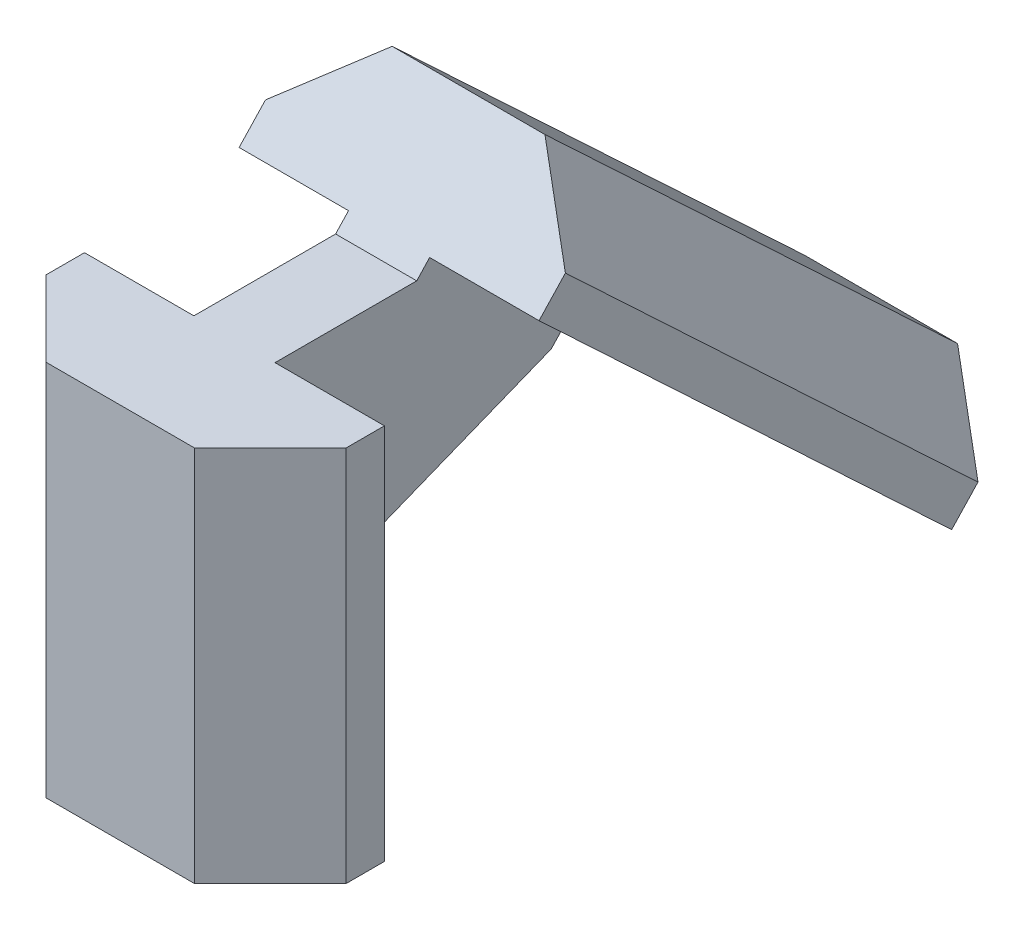
SolidWorks part; units mm, degrees
ref_plane "Front Plane" through (0, 0, 0) normal (0, 0, 1) x (1, 0, 0)
ref_plane "Top Plane" through (0, 0, 0) normal (0, 1, 0) x (1, 0, 0)
ref_plane "Right Plane" through (0, 0, 0) normal (1, 0, 0) x (0, 0, -1)
sketch "Sketch1" plane through (0, 0, 0) normal (0, 1, 0) x (1, 0, 0)
  line L0 (-3.9407, -6.0493) -> (3.9407, -6.0493)
  line L1 (7.95, 0) -> (7.95, -2.04)
  line L2 (7.95, -2.04) -> (3.9407, -6.0493)
  line L4 (0, 0) -> (0, 4.5954) construction
  line L5 (-7.95, -2.04) -> (-3.9407, -6.0493)
  line L6 (-7.95, 0) -> (-7.95, -2.04)
  line L7 (-7.95, 0) -> (7.95, 0)
  point P6 (3.7791, -6.0493)
  dimension "D1" = 15.9
  dimension "D2" = 2.04
  dimension "D3" = 5.67
extrude "Boss-Extrude1" add sketch "Sketch1" against normal blind 20 contours L7 L1 L2 L0 L5 L6
ref_plane "Plane1" through (0, 0, 0) normal (1, 0, 0) x (0, 0, -1)
sketch "Sketch2" plane through (0, 0, 0) normal (1, 0, 0) x (0, 0, -1)
  line L10 (4.1546, 0) -> (20.6216, -15.4568)
  line L12 (4.1546, 0) -> (5.7276, 1.6758)
  line L13 (5.7276, 1.6758) -> (22.1946, -13.781)
  line L14 (22.1946, -13.781) -> (20.6216, -15.4568)
  point P0 (20.7767, -15.2916)
  point P5 (14.9625, -10.1448)
sketch "Sketch4" plane through (0, 0, 0) normal (1, 0, 0) x (0, 0, -1)
  line L0 (0, 0) -> (7.513, 0)
  line L1 (5.7276, 1.6758) -> (22.1946, -13.781) construction
  line L2 (7.513, 0) -> (14.6438, -6.6935)
  line L3 (14.6438, -6.6935) -> (0, -12.5397)
  line L4 (0, -20) -> (0, 0) construction
  line L5 (0, -12.5397) -> (0, 0)
  point P6 (11.2016, -3.4624)
  point P11 (0, 0)
  point P12 (14.6438, -6.6935)
  point P13 (0, -12.5397)
extrude "Boss-Extrude3" add sketch "Sketch4" along normal mid plane 4.3 contours L5 L0 L2 L3
ref_plane "Plane2" through (0, 4.4781, -4.2034) normal (0, 0.7291, -0.6844) x (1, 0, 0)
sketch "Sketch6" plane through (0, 4.4781, -4.2034) normal (0, 0.7291, -0.6844) x (1, 0, 0)
  line L0 (-2.15, 15.258) -> (2.15, 15.258)
  line L1 (2.15, 15.258) -> (2.15, 5.4778)
  line L2 (2.15, 5.4778) -> (-2.15, 5.4778)
  line L3 (-2.15, 5.4778) -> (-2.15, 15.258)
extrude "Boss-Extrude4" add sketch "Sketch6" against normal up to surface (1 mm away) contours L3 L0 L1 L2 up to face at (0, -3.3467, -11.0784)
ref_plane "Plane3" through (0, -3.749, -3.994) normal (0, 0.6844, 0.7291) x (1, 0, 0)
sketch "Sketch8" plane through (0, -3.749, -3.994) normal (0, 0.6844, 0.7291) x (1, 0, 0)
  line L0 (-4.05, 12.2975) -> (4.05, 12.2975)
  line L1 (55, 6.1418) -> (-55, 6.1418) construction
  line L2 (7.95, 6.1418) -> (7.95, 8.1818)
  line L3 (7.95, 8.1818) -> (4.05, 12.2975)
  line L4 (-7.95, 6.1418) -> (-7.95, 8.1818)
  line L5 (0, 6.1418) -> (0, 14.4021) construction
  line L6 (-7.95, 8.1818) -> (-4.05, 12.2975)
  line L7 (7.95, 6.1418) -> (-7.95, 6.1418)
  dimension "D1" = 15.9
  dimension "D2" = 5.67
  dimension "D3" = 2.04
  dimension "D4" = 8.1
extrude "Boss-Extrude5" add sketch "Sketch8" against normal blind 30 contours L7 L4 L6 L0 L3 L2
